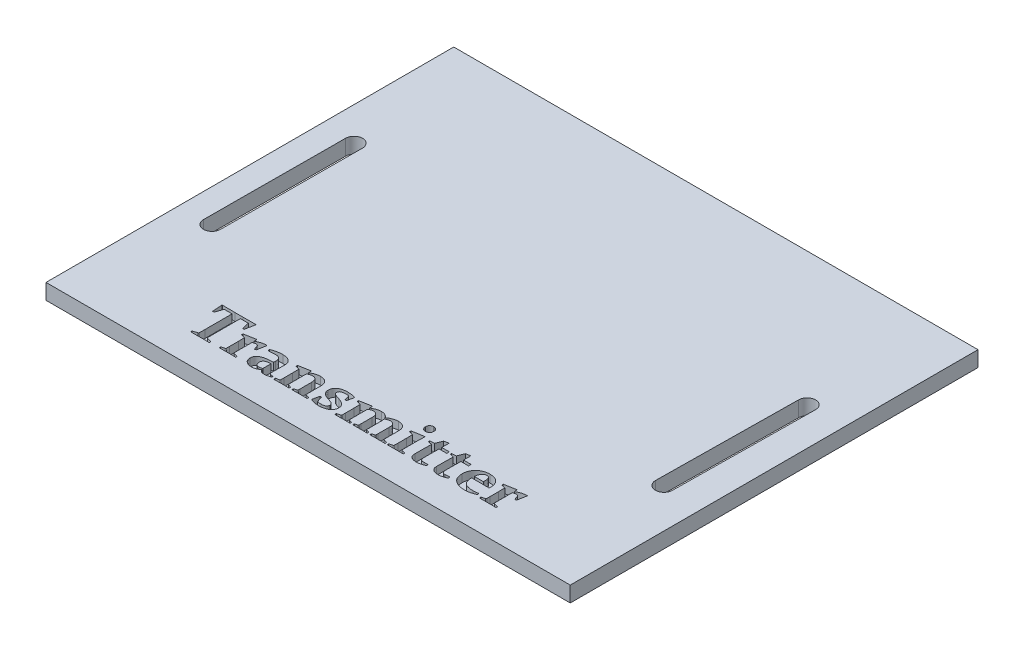
SolidWorks part; units mm, degrees
ref_plane "Front Plane" through (0, 0, 0) normal (0, 0, 1) x (1, 0, 0)
ref_plane "Top Plane" through (0, 0, 0) normal (0, 1, 0) x (1, 0, 0)
ref_plane "Right Plane" through (0, 0, 0) normal (1, 0, 0) x (0, 0, -1)
sketch "Sketch1" plane through (0, 0, 0) normal (0, 1, 0) x (1, 0, 0)
  line L1 (-42.8625, 33.3375) -> (42.8625, 33.3375)
  line L2 (-42.8625, 33.3375) -> (-42.8625, -33.3375)
  line L3 (-42.8625, -33.3375) -> (42.8625, -33.3375)
  line L4 (42.8625, 33.3375) -> (42.8625, -33.3375)
  line L5 (-42.8625, 33.3375) -> (42.8625, -33.3375) construction
  line L6 (-42.8625, -33.3375) -> (42.8625, 33.3375) construction
  line L8 (-42.8625, 15.3624) -> (-42.8625, 0.1224)
  point P0 (0, 0)
  dimension "D1" = 85.725
  dimension "D2" = 66.675
extrude "Boss-Extrude2" add sketch "Sketch1" along normal blind 2.54 contours L1 L4 L3 L2
hole_wizard "7/64 (0.10938) Diameter Slot1" positions "Sketch3" profile "Sketch4" size "7/64" standard "ANSI Inch" slot yes end condition through all
sketch "Sketch3" plane through (0, 2.54, 0) normal (0, 1, 0) x (1, 0, 0)
  line L0 (36.3915, -12.953) -> (36.7084, 12.953) construction
  point P0 (36.5499, 0)
  dimension "D1" = 25.908
sketch "Sketch4" plane through (36.5499, 2.54, 0) normal (1, 0, 0) x (0, 0, 1)
  line L0 (0, 0) -> (0, 2.54)
  line L1 (0, 2.54) -> (1.3891, 2.54)
  line L2 (1.3891, 2.54) -> (1.3891, 0)
  line L5 (1.3891, 0) -> (0, 0)
  line L11 (0, -6.35) -> (0, 107.95) construction
  dimension "Thru Hole Dia." = 2.7783
  dimension "Thru Hole Depth" = 2.54
hole_wizard "7/64 (0.10938) Diameter Slot2" positions "Sketch5" profile "Sketch6" size "7/64" standard "ANSI Inch" slot yes end condition through all
sketch "Sketch5" plane through (0, 2.54, 0) normal (0, 1, 0) x (1, 0, 0)
  line L0 (-37.5028, -12.9539) -> (-37.3843, 12.9539) construction
  point P0 (-37.4436, 0)
  point P9 (-37.4436, 0)
  dimension "D1" = 25.908
sketch "Sketch6" plane through (-37.4436, 2.54, 0) normal (1, 0, 0) x (0, 0, 1)
  line L0 (0, 0) -> (0, 2.54)
  line L1 (0, 2.54) -> (1.3891, 2.54)
  line L2 (1.3891, 2.54) -> (1.3891, 0)
  line L5 (1.3891, 0) -> (0, 0)
  line L11 (0, -6.35) -> (0, 107.95) construction
  dimension "Thru Hole Dia." = 2.7783
  dimension "Thru Hole Depth" = 2.54
sketch "Sketch8" plane through (0, 2.54, 0) normal (0, 1, 0) x (1, 0, 0)
  text T0 "Transmitter\r\n" font "Constantia" height in points 24
  point P1 (0, 0)
extrude "Cut-Extrude2" cut sketch "Sketch8" against normal blind 1.27
equation "\"3.00mmin\"=3"
equation "\"3.00inn\"=3"
equation "\"0.50inn\"=0.1"
